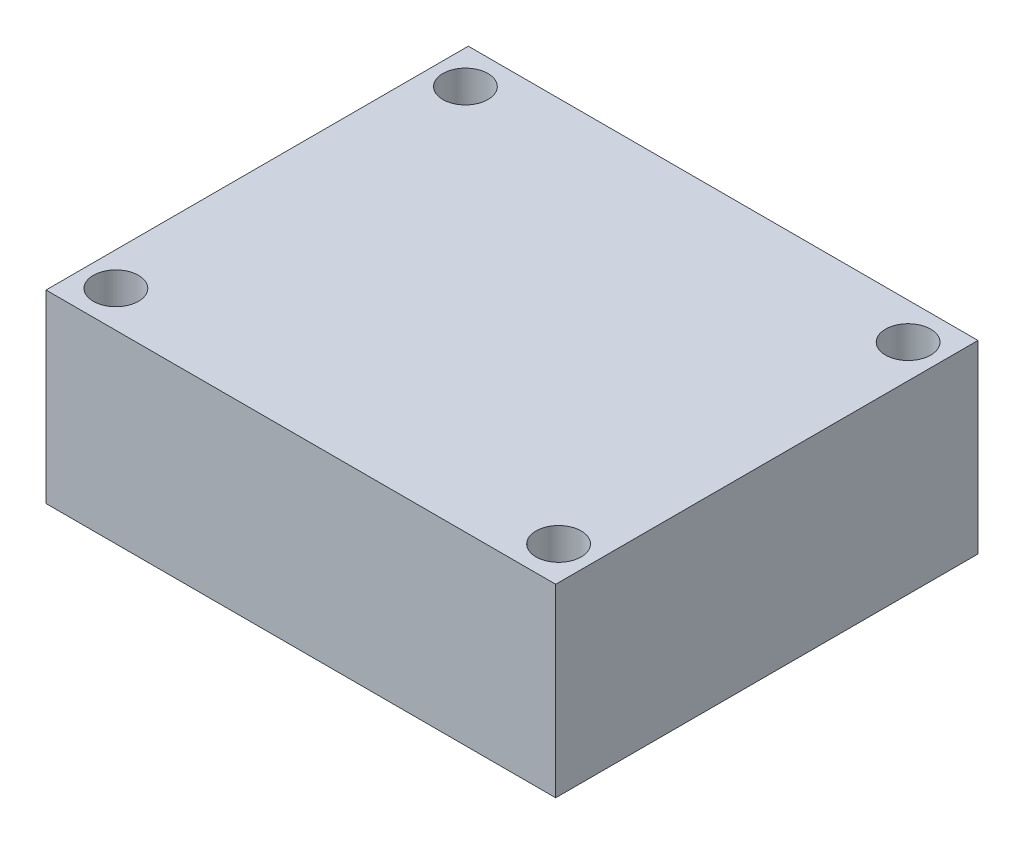
SolidWorks part; units mm, degrees
material "ABS"
ref_plane "Front Plane" through (0, 0, 0) normal (0, 0, 1) x (1, 0, 0)
ref_plane "Top Plane" through (0, 0, 0) normal (0, 1, 0) x (1, 0, 0)
ref_plane "Right Plane" through (0, 0, 0) normal (1, 0, 0) x (0, 0, -1)
sketch "Sketch1" plane through (0, 0, 0) normal (0, 1, 0) x (1, 0, 0)
  line L0 (0, 0) -> (0, 5.7699) construction
  line L1 (-17.5, 14.5) -> (17.5, 14.5)
  line L2 (-17.5, 14.5) -> (-17.5, -14.5)
  line L3 (-17.5, -14.5) -> (17.5, -14.5)
  line L4 (17.5, 14.5) -> (17.5, -14.5)
  line L5 (-17.5, 14.5) -> (17.5, -14.5) construction
  line L6 (-17.5, -14.5) -> (17.5, 14.5) construction
  line L7 (0, 0) -> (-7.7865, 0) construction
  circle A0 centre (-15.2, 12) radius 1.55
  circle A1 centre (15.2, 12) radius 1.55
  circle A2 centre (-15.2, -12) radius 1.55
  circle A3 centre (15.2, -12) radius 1.55
  point P0 (0, 0)
  dimension "D3" = 3.1
  dimension "D4" = 2.5
  dimension "D5" = 2.3
  dimension "D1" = 35
  dimension "D2" = 29
extrude "Boss-Extrude1" add sketch "Sketch1" along normal blind 12.7
